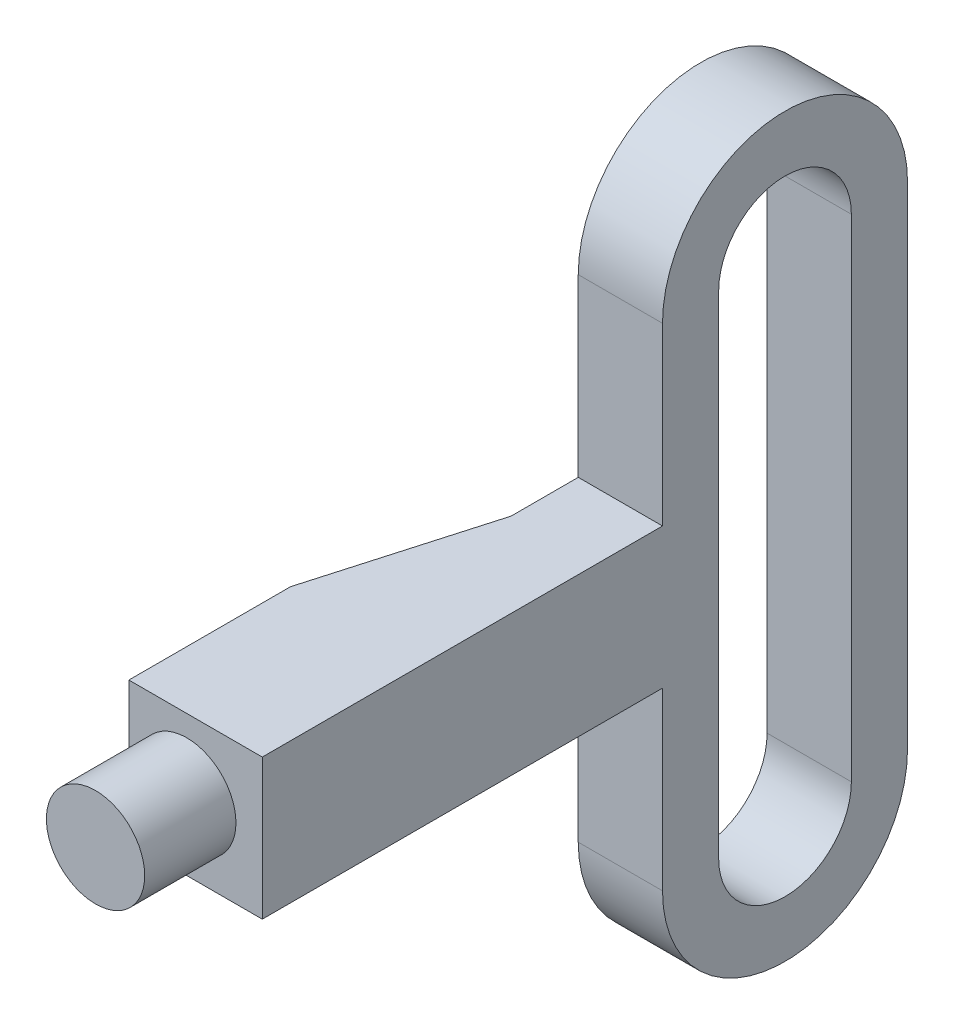
SolidWorks part; units mm, degrees
ref_plane "Front Plane" through (0, 0, 0) normal (0, 0, 1) x (1, 0, 0)
ref_plane "Top Plane" through (0, 0, 0) normal (0, 1, 0) x (1, 0, 0)
ref_plane "Right Plane" through (0, 0, 0) normal (1, 0, 0) x (0, 0, -1)
sketch "Sketch2" plane through (0, 0, 0) normal (1, 0, 0) x (0, 0, -1)
  line L0 (-22.16, -44.45) -> (-22.16, 44.45)
  line L1 (0, -44.45) -> (0, 44.45) construction
  line L2 (-12, -44.45) -> (-12, 44.45)
  line L3 (12, -44.45) -> (12, 44.45)
  line L4 (22.16, -44.45) -> (22.16, 44.45)
  line L5 (0, 0) -> (-80.0365, 0) construction
  line L6 (-22.16, -12.7) -> (-111.06, -12.7)
  line L7 (-22.16, 0) -> (-111.06, 0) construction
  line L8 (-22.16, 0) -> (-22.16, 12.7)
  line L9 (-22.16, 12.7) -> (-111.06, 12.7)
  line L10 (-111.06, -12.7) -> (-111.06, 12.7)
  arc A0 (-12, -44.45) -> (12, -44.45) centre (0, -44.45) ccw
  arc A1 (12, 44.45) -> (-12, 44.45) centre (0, 44.45) ccw
  arc A2 (22.16, 44.45) -> (-22.16, 44.45) centre (0, 44.45) ccw
  arc A3 (-22.16, -44.45) -> (22.16, -44.45) centre (0, -44.45) ccw
  point P5 (0, 0)
  point P16 (-40.0182, 0)
  dimension "D2" = 12
  dimension "D1" = 88.9
  dimension "D4" = 88.9
  dimension "D5" = 25.4
  dimension "D3" = 10.16
extrude "Boss-Extrude2" add sketch "Sketch2" along normal blind 24.13 contours L10 L6 L0 L9 | L0 A3 L4 A2 A1 L3 A0 L2 region at (0, -28.575, 20.756) region at (0, 0, 66.61)
sketch "Sketch3" plane through (0, 0, 111.06) normal (0, 0, 1) x (1, 0, 0)
  line L0 (0, 0) -> (24.13, 0) construction
  line L1 (0, -12.7) -> (0, 12.7) construction
  line L2 (24.13, -12.7) -> (24.13, 12.7) construction
  line L7 (0, 12.7) -> (0, -12.7)
  line L8 (0, -12.7) -> (24.13, -12.7)
  line L9 (24.13, -12.7) -> (24.13, 12.7)
  line L10 (24.13, 12.7) -> (0, 12.7)
  line L11 (0, 12.7) -> (0, -12.7)
  line L12 (0, -12.7) -> (24.13, -12.7)
  line L13 (24.13, -12.7) -> (24.13, 12.7)
  line L14 (24.13, 12.7) -> (0, 12.7)
  circle A1 centre (10.4775, 0) radius 13.6525 construction
  circle A2 centre (10.4775, 0) radius 8.89
  dimension "D1" = 27.305
  dimension "D3" = 17.78
  dimension "D2" = 0
extrude "Cut-Extrude3" cut sketch "Sketch3" against normal blind 16.51
sketch "Sketch4" plane through (0, 0, 0) normal (-1, 0, 0) x (0, 0, 1)
  line L1 (-69.1853, 78.6449) -> (69.1853, 78.6449)
  line L2 (-69.1853, 78.6449) -> (-69.1853, -78.6449)
  line L3 (-69.1853, -78.6449) -> (69.1853, -78.6449)
  line L4 (69.1853, 78.6449) -> (69.1853, -78.6449)
  line L5 (-69.1853, 78.6449) -> (69.1853, -78.6449) construction
  line L6 (-69.1853, -78.6449) -> (69.1853, 78.6449) construction
  point P0 (0, 0)
extrude "Cut-Extrude4" cut sketch "Sketch4" against normal blind 8.89
chamfer "Chamfer1" distance 10 angle 74 1 edges at (8.89, 0, 69.1853) first distance on face at (4.445, 0, 69.1853)
